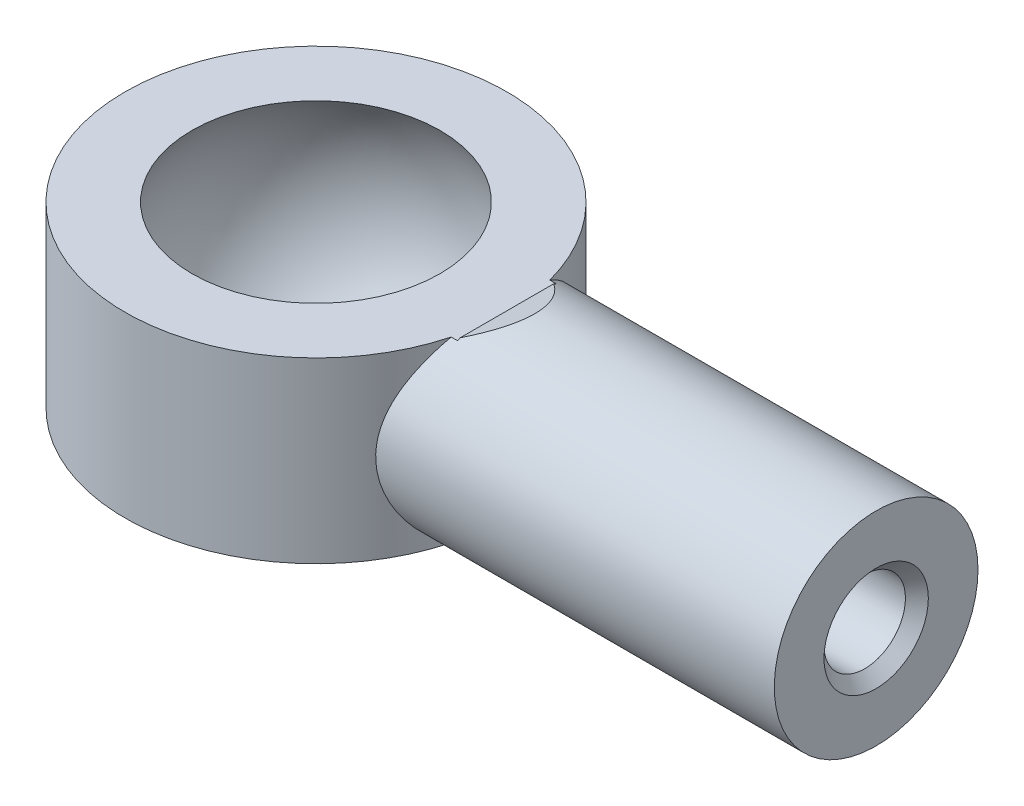
SolidWorks part; units mm, degrees
other "标注1"
sketch "草图11" plane through (-3.75, 2, -3.75) normal (-0.0131, 0.9998, -0.0148) x (-0.4755, -0.0193, -0.8795)
ref_plane "前视基准面" through (0, 0, 0) normal (0, 0, 1) x (1, 0, 0)
ref_plane "上视基准面" through (0, 0, 0) normal (0, 1, 0) x (1, 0, 0)
ref_plane "右视基准面" through (0, 0, 0) normal (1, 0, 0) x (0, 0, -1)
other "Configuration Table"
sketch "草图1" plane through (0, 0, 0) normal (0, 1, 0) x (1, 0, 0)
  circle A1 centre (0, 0) radius 3.75
  dimension "D1" = 7.5
extrude "凸台-拉伸2" add sketch "草图1" along normal mid plane 3.5
ref_plane "基准面1" through (3.75, 0, 0) normal (1, 0, 0) x (0, 0, -1)
sketch "草图2" plane through (3.75, 0, 0) normal (1, 0, 0) x (0, 0, -1)
  circle A0 centre (0, 0) radius 2
  dimension "D1" = 4
extrude "凸台-拉伸3" add sketch "草图2" along normal blind 7.25
hole_wizard "M2 螺纹孔1" positions "草图5" profile "草图6" tap size "M2" standard "GB"
sketch "草图5" plane through (11, 0, 0) normal (1, 0, 0) x (0, 0, -1)
  point P0 (0, 0)
sketch "草图6" plane through (11, 0, 0) normal (0, 1, 0) x (0, 0, -1)
  line L0 (0, 0) -> (0, 5.6807)
  line L1 (0, 5.6807) -> (0.8, 5.2)
  line L2 (0.8, 5.2) -> (0.8, 0.225)
  line L3 (0.8, 0.225) -> (1.025, 0)
  line L5 (1.025, 0) -> (0, 0)
  line L6 (-0.8, 0.225) -> (-1.025, 0) construction
  line L10 (0, 5.6807) -> (-0.8, 5.2) construction
  line L11 (0, -6.35) -> (0, 107.95) construction
  dimension "螺纹孔钻头直径" = 1.6
  dimension "螺纹孔钻头深度" = 5.2
  dimension "近端锥形沉头孔直径" = 2.05
  dimension "近端锥形沉头孔角度" = 90
  dimension "导头角度" = 118
cosmetic thread "孔螺蚊线1" parameters "D1"=4, "D2"=2
sketch "草图7" plane through (0, 1.75, 0) normal (0, 1, 0) x (1, 0, 0)
  circle A0 centre (0, 0) radius 1.5
  dimension "D1" = 3
extrude "切除-拉伸1" cut sketch "草图7" against normal mid plane 7.5
sketch "草图8" plane through (3.75, 0, 0) normal (-1, 0, 0) x (0, 0, 1)
  line L0 (-0.9682, 1.75) -> (0.9682, 1.75)
  line L1 (3.75, 1.75) -> (-3.75, 1.75) construction
  line L2 (-0.9682, -1.75) -> (0.9682, -1.75)
  line L3 (-3.75, -1.75) -> (3.75, -1.75) construction
  arc A0 (0.9682, -1.75) -> (0.9682, 1.75) centre (0, 0) ccw
  arc A1 (-0.9682, 1.75) -> (-0.9682, -1.75) centre (0, 0) ccw
  dimension "D1" = 2
extrude "凸台-拉伸4" add sketch "草图8" along normal up to surface (0.1272 mm away) up to face at (0, -1.75, 3.75)
sketch "草图9" plane through (0, 0, 0) normal (0, 0, 1) x (1, 0, 0)
  line L1 (3.6228, 1.75) -> (3.75, 1.75) construction
  line L3 (3.75, -1.925) -> (3.75, 1.925) construction
  line L4 (11, 2) -> (3.75, 2) construction
  line L5 (3.75, 2) -> (3.6864, 1.75)
  line L6 (3.6864, 1.75) -> (4.2974, 2)
  line L7 (4.2974, 2) -> (3.75, 2)
  line L8 (4.125, 0) -> (-4.125, 0) construction
  line L9 (3.75, -2) -> (3.6864, -1.75)
  line L10 (3.6864, -1.75) -> (4.2974, -2)
  line L11 (4.2974, -2) -> (3.75, -2)
  dimension "D1" = 0.6601
extrude "切除-拉伸2" cut sketch "草图9" against normal mid plane 7.5
sketch "草图10" plane through (0, 0, 0) normal (0, 1, 0) x (1, 0, 0)
  line L0 (-4.2936, 0) -> (4.6778, 0) construction
  line L1 (-3, 0) -> (3, 0)
  arc A0 (3, 0) -> (-3, 0) centre (0, 0) ccw
  dimension "D1" = 6
revolve "切除-旋转1" cut sketch "草图10" angle 360 about L0
